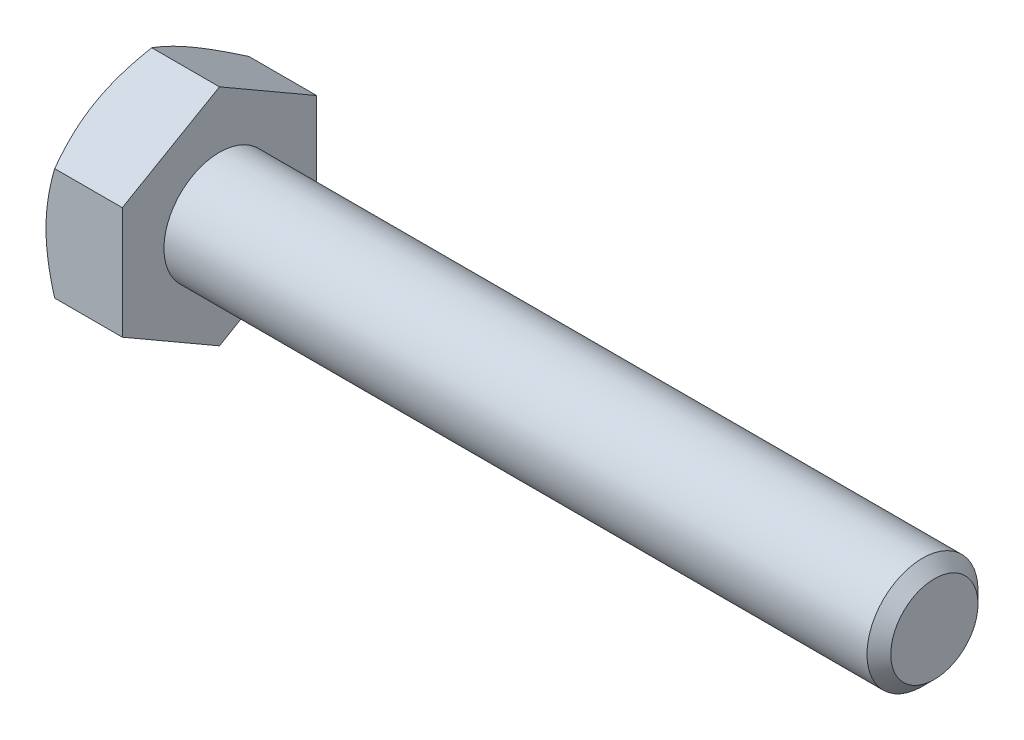
SolidWorks part; units mm, degrees
material "Alloy Steel"
ref_plane "Front Plane" through (0, 0, 0) normal (0, 0, 1) x (1, 0, 0)
ref_plane "Top Plane" through (0, 0, 0) normal (0, 1, 0) x (1, 0, 0)
ref_plane "Right Plane" through (0, 0, 0) normal (1, 0, 0) x (0, 0, -1)
sketch "Sketch1" plane through (0, 0, 0) normal (0, 0, 1) x (1, 0, 0)
  line L0 (-22.6298, 0) -> (22.6298, 0) construction
  line L1 (22.6298, 3.175) -> (22.6298, -3.175) construction
  line L2 (-18.2642, 5.5562) -> (-18.2642, -5.5562) construction
  line L3 (-22.6298, 5.5562) -> (-22.6298, -5.5562) construction
  point P9 (-18.2642, 0)
  point P10 (19.4548, -3.175)
  dimension "Screw Dia" = 6.35
  dimension "Hex" = 11.1125
  dimension "Head Ht" = 4.3656
  dimension "Screw Lenght" = 40.894
  dimension "D1" = 3.175
ref_plane "Plane2" through (22.6298, 0, 0) normal (1, 0, 0) x (0, 0, -1)
sketch "Sketch5" plane through (22.6298, 0, 0) normal (1, 0, 0) x (0, 0, -1)
  circle A0 centre (0, 0) radius 3.175
extrude "Boss-Extrude3" add sketch "Sketch5" against normal up to vertex (40.894 mm away) up to point (-18.2642, 0, 0)
sketch "Sketch9" plane through (22.6298, 0, 0) normal (1, 0, 0) x (0, 0, -1)
  circle A1 centre (0, 0) radius 3.175
  circle A2 centre (0, 0) radius 3.175
  dimension "D1" = 0
curve "Helix/Spiral1" [suppressed] pitch 0.9071 height 19.9571 turns 22 parameters "Pitch"=0.9071
chamfer "Chamfer1" distance 0.6804 angle 45 1 edges at (22.6298, 0, -3.175)
sketch "Sketch10" plane through (0, 0, 0) normal (0, 0, 1) x (1, 0, 0)
  line L0 (22.6298, 3.175) -> (22.97, 2.5858)
  line L1 (22.97, 2.5858) -> (23.0834, 2.5858)
  line L2 (23.0834, 2.5858) -> (23.4236, 3.175)
  line L3 (22.6298, 3.175) -> (23.4236, 3.175)
  line L4 (23.0267, 3.175) -> (23.0267, 2.5858) construction
  line L5 (22.7999, 2.8804) -> (23.2535, 2.8804) construction
  dimension "D1" = 60
  dimension "D2" = 0.1134
  dimension "D3" = 0.4536
sweep "Cut-Sweep1" [suppressed] cut profiles "Sketch10" path "Helix/Spiral1"
sketch "Sketch11" plane through (0, 0, 0) normal (0, 0, 1) x (1, 0, 0)
  line L0 (-18.2642, 3.175) -> (-18.2642, 0)
  line L1 (-18.2642, 0) -> (6.7548, 0)
  line L3 (6.7548, 0) -> (3.5798, 3.175)
  line L4 (-18.2642, 3.175) -> (3.5798, 3.175)
  dimension "D1" = 45
  dimension "MIn Thread" = 19.05
revolve "Revolve1" [suppressed] add sketch "Sketch11" angle 360 about L1
sketch "Sketch6" plane through (-18.2642, 0, 0) normal (-1, 0, 0) x (0, 0, 1)
  line L0 (0, 5.5562) -> (0, -5.5562) construction
  line L1 (5.5563, 3.2079) -> (0, 6.4158)
  line L2 (0, 6.4158) -> (-5.5562, 3.2079)
  line L3 (-5.5562, 3.2079) -> (-5.5562, -3.2079)
  line L4 (-5.5562, -3.2079) -> (0, -6.4158)
  line L5 (0, -6.4158) -> (5.5563, -3.2079)
  line L6 (5.5563, -3.2079) -> (5.5563, 3.2079)
  circle A0 centre (0, 0) radius 5.5562 construction
extrude "Boss-Extrude4" add sketch "Sketch6" along normal up to vertex (4.3656 mm away) up to point (-22.6298, -5.5562, 0)
sketch "Sketch7" plane through (-22.6298, 0, 0) normal (-1, 0, 0) x (0, 0, 1)
  circle A0 centre (0, 0) radius 5.5562 construction
  circle A1 centre (0, 0) radius 5.5562
sketch "Sketch8" plane through (-22.6298, 0, 0) normal (-1, 0, 0) x (0, 0, 1)
  circle A0 centre (0, 0) radius 5.5562 construction
  circle A1 centre (0, 0) radius 5.5562
extrude "Cut-Extrude3" cut sketch "Sketch8" against normal through all draft 60 flip side to cut
sketch "Sketch12" plane through (-22.6298, 0, 0) normal (-1, 0, 0) x (0, 0, 1)
  line L0 (0, 4.2783) -> (0, 2.3892) construction
  line L1 (0.1667, 4.2783) -> (0.1667, 2.3892)
  line L2 (-0.1667, 4.2783) -> (-0.1667, 2.3892)
  line L3 (0, 3.175) -> (0, -3.175) construction
  arc A0 (0.1667, 4.2783) -> (-0.1667, 4.2783) centre (0, 4.2783) ccw
  arc A1 (-0.1667, 2.3892) -> (0.1667, 2.3892) centre (0, 2.3892) ccw
  circle A3 centre (0, 0) radius 2.2225 construction
  circle A4 centre (0, 0) radius 4.445 construction
  point P2 (0, 3.3337)
  dimension "D1" = 4.445
  dimension "D3" = 8.89
  dimension "D2" = 0.3334
extrude "Cut-Extrude4" [suppressed] cut sketch "Sketch12" against normal blind 0.254
pattern_circular "CirPattern1" [suppressed] count 6 over 360 of bodies 116
equation "\"D2@Sketch10\" = \"Pitch@Helix/Spiral1\"*.125"
equation "\"D3@Sketch10\" = \"Pitch@Helix/Spiral1\"*.5"
equation "\"D3@Helix/Spiral1\" = \"MIn Thread@Sketch11\"+\"Pitch@Helix/Spiral1\""
equation "\"D1@Chamfer1\" = \"Pitch@Helix/Spiral1\"*.75"
equation "\"D1@Sketch12\" = \"Hex@Sketch1\"*.4"
equation "\"D3@Sketch12\" = \"Hex@Sketch1\"*.8"
equation "\"D2@Sketch12\" = \"Hex@Sketch1\"*.03"
equation "\"D1@Sketch1\" = \"Pitch@Helix/Spiral1\"*3.5"
